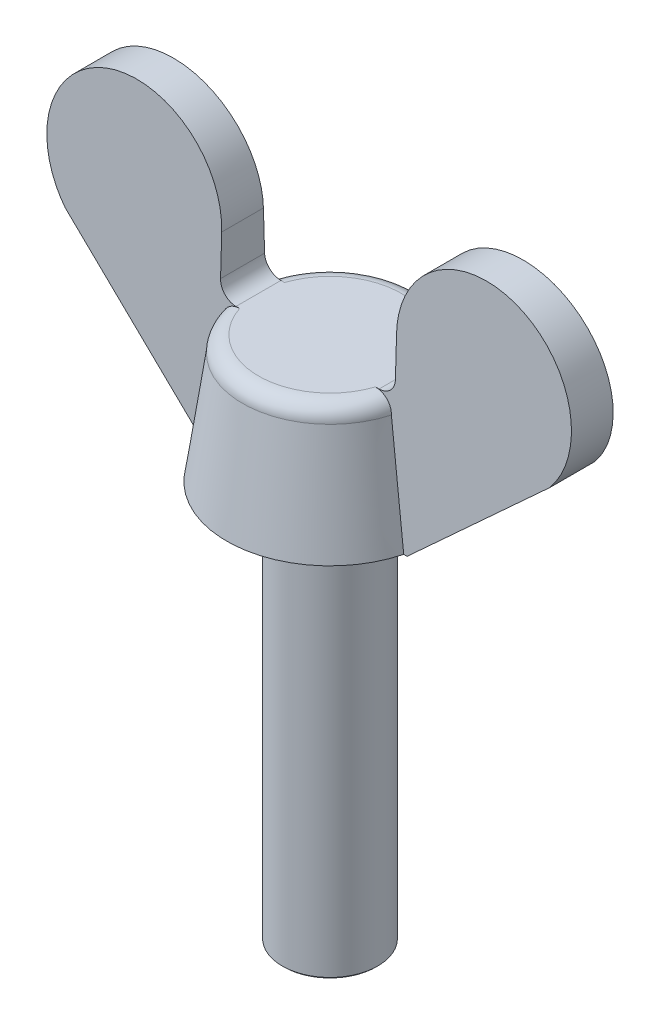
SolidWorks part; units mm, degrees
ref_plane "Front Plane" through (0, 0, 0) normal (0, 0, 1) x (1, 0, 0)
ref_plane "Top Plane" through (0, 0, 0) normal (0, 1, 0) x (1, 0, 0)
ref_plane "Right Plane" through (0, 0, 0) normal (1, 0, 0) x (0, 0, -1)
sketch "Sketch1" plane through (0, 0, 0) normal (0, 0, 1) x (1, 0, 0)
  line L0 (0, 0) -> (0, 51.4263) construction
  line L2 (-6.5, 0) -> (-15.2426, 8)
  line L4 (-4.5, 8) -> (4.5, 8)
  line L5 (-6.5, 0) -> (6.5, 0)
  line L10 (-5.5, 9) -> (-5.5, 11.5)
  line L11 (5.5, 9) -> (5.5, 11.5)
  line L12 (6.5, 0) -> (15.2426, 8)
  arc A1 (-5.5, 9) -> (-4.5, 8) centre (-4.5, 9) ccw
  arc A4 (-15.2426, 8) -> (-5.5, 11.5) centre (-11, 11.5) cw
  arc A5 (5.5, 9) -> (4.5, 8) centre (4.5, 9) cw
  arc A6 (15.2426, 8) -> (5.5, 11.5) centre (11, 11.5) ccw
  point P3 (-16.5, 11.5)
  point P10 (-11, 17)
  point P13 (11, 17)
  point P19 (0, 0)
  point P20 (0, 8)
  point P40 (16.5, 11.5)
  dimension "D1" = 17
  dimension "R3" = 1
  dimension "M" = 8
  dimension "D2_2" = 13
  dimension "e" = 33
  dimension "D3 MIN " = 9
extrude "Boss-Extrude1" add sketch "Sketch1" along normal blind 1.65 and the other way blind 1.65
sketch "Sketch6" plane through (0, 0, 0) normal (1, 0, 0) x (0, 0, -1)
  line L5 (0, 0) -> (0, 14) construction
  line L7 (-3, 0) -> (-1.65, 0)
  line L8 (-1.65, 0) -> (-1.15, 17)
  line L9 (1.65, 17) -> (-1.65, 17) construction
  line L10 (-1.15, 17) -> (-3, 17)
  line L11 (-3, 17) -> (-3, 0)
  line L12 (1.15, 17) -> (3, 17)
  line L13 (3, 0) -> (1.65, 0)
  line L14 (1.65, 0) -> (1.15, 17)
  line L15 (3, 17) -> (3, 0)
  dimension "D1" = 3.3
  dimension "D2" = 2.3
  dimension "D3" = 6
extrude "Cut-Extrude2" cut sketch "Sketch6" against normal blind 103 and the other way blind 81
sketch "Sketch2" plane through (0, 0, 0) normal (1, 0, 0) x (0, 0, -1)
  line L0 (0, 0) -> (0, 17) construction
  line L1 (1.15, 17) -> (-1.15, 17) construction
  line L2 (0, 0) -> (-6.5, 0)
  line L3 (-6.5, 0) -> (-5.5, 7)
  line L4 (-4.5, 8) -> (0, 8)
  line L5 (0, 8) -> (0, 0)
  line L6 (1.4147, 8) -> (-1.4147, 8) construction
  arc A0 (-5.5, 7) -> (-4.5, 8) centre (-4.5, 7) cw
  dimension "D2" = 1
  dimension "d_2" = 13
  dimension "D_3" = 11
revolve "Revolve1" add sketch "Sketch2" angle 360 about L0
sketch "Sketch7" plane through (0, 0, 0) normal (1, 0, 0) x (0, 0, -1)
  line L0 (0, 0) -> (0, -25) construction
  line L1 (0, -25) -> (-2.9, -25)
  line L2 (-2.9, -25) -> (-3, -24.9)
  line L3 (-3, -24.9) -> (-3, 0)
  line L4 (-6.5, 0) -> (-1.65, 0) construction
  line L5 (-3, 0) -> (0, 0)
  line L6 (1.65, 0) -> (6.5, 0) construction
  line L7 (0, -25) -> (0, 0)
  dimension "LENGTH" = 25
  dimension "D2" = 45
  dimension "HOLE2" = 5.8
  dimension "HOLE1" = 6
revolve "Revolve2" add sketch "Sketch7" angle 360 about L0
cosmetic thread "Cosmetic Thread1" parameters "D2"=6
